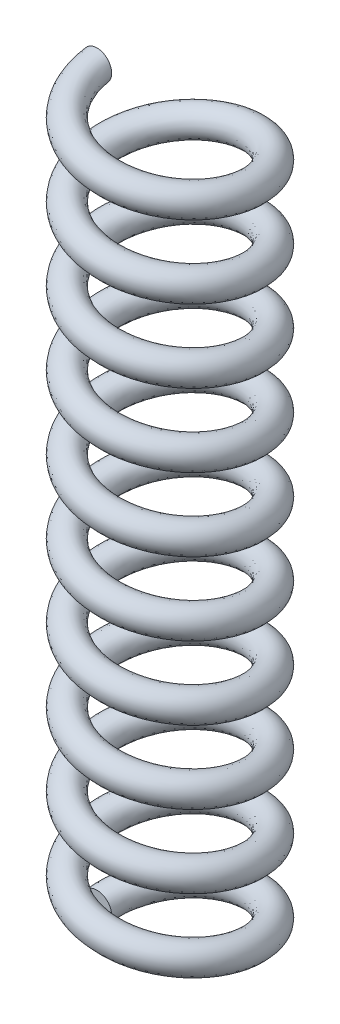
SolidWorks part; units mm, degrees
material "Alliage 1060"
ref_plane "Plan de face" through (0, 0, 0) normal (0, 0, 1) x (1, 0, 0)
ref_plane "Plan de dessus" through (0, 0, 0) normal (0, 1, 0) x (1, 0, 0)
ref_plane "Plan de droite" through (0, 0, 0) normal (1, 0, 0) x (0, 0, -1)
sketch "Esquisse1" plane through (0, 0, 0) normal (0, 1, 0) x (1, 0, 0)
  circle A0 centre (0, 0) radius 10
  dimension "D1" = 20
curve "Hélice/Spirale2" pitch 10 height 100 turns 10
sketch "Esquisse4" plane through (0, 0, 0) normal (0, 0, 1) x (1, 0, 0)
  circle A0 centre (-10, 0) radius 2
  spline S0 degree 3 poles (-10, 0) (-10, 0.207) (-9.4793, 0.6256) (-7.2552, 1.2498) (-3.9265, 1.875) (0, 2.5) (3.9265, 3.125) (7.2552, 3.75) (9.4793, 4.375) (10.2603, 5) (9.4793, 5.625) (7.2552, 6.25) (2.8169, 7.0833) (-2.8169, 7.9167) (-7.2552, 8.75) (-9.4793, 9.375) (-10.2603, 10) (-9.4793, 10.625) (-7.2552, 11.25) (-2.8169, 12.0833) (2.8169, 12.9167) (7.2552, 13.75) (9.4793, 14.375) (10.2603, 15) (9.4793, 15.625) (7.2552, 16.25) (2.8169, 17.0833) (-2.8169, 17.9167) (-7.2552, 18.75) (-9.4793, 19.375) (-10.2603, 20) (-9.4793, 20.625) (-7.2552, 21.25) (-2.8169, 22.0833) (2.8169, 22.9167) (7.2552, 23.75) (9.4793, 24.375) (10.2603, 25) (9.4793, 25.625) (7.2552, 26.25) (2.8169, 27.0833) (-2.8169, 27.9167) (-7.2552, 28.75) (-9.4793, 29.375) (-10.2603, 30) (-9.4793, 30.625) (-7.2552, 31.25) (-2.8169, 32.0833) (2.8169, 32.9167) (7.2552, 33.75) (9.4793, 34.375) (10.2603, 35) (9.4793, 35.625) (7.2552, 36.25) (2.8169, 37.0833) (-2.8169, 37.9167) (-7.2552, 38.75) (-9.4793, 39.375) (-10.2603, 40) (-9.4793, 40.625) (-7.2552, 41.25) (-2.8169, 42.0833) (2.8169, 42.9167) (7.2552, 43.75) (9.4793, 44.375) (10.2603, 45) (9.4793, 45.625) (7.2552, 46.25) (2.8169, 47.0833) (-2.8169, 47.9167) (-7.2552, 48.75) (-9.4793, 49.375) (-10.2603, 50) (-9.4793, 50.625) (-7.2552, 51.25) (-2.8169, 52.0833) (2.8169, 52.9167) (7.2552, 53.75) (9.4793, 54.375) (10.2603, 55) (9.4793, 55.625) (7.2552, 56.25) (2.8169, 57.0833) (-2.8169, 57.9167) (-7.2552, 58.75) (-9.4793, 59.375) (-10.2603, 60) (-9.4793, 60.625) (-7.2552, 61.25) (-2.8169, 62.0833) (2.8169, 62.9167) (7.2552, 63.75) (9.4793, 64.375) (10.2603, 65) (9.4793, 65.625) (7.2552, 66.25) (2.8169, 67.0833) (-2.8169, 67.9167) (-7.2552, 68.75) (-9.4793, 69.375) (-10.2603, 70) (-9.4793, 70.625) (-7.2552, 71.25) (-2.8169, 72.0833) (2.8169, 72.9167) (7.2552, 73.75) (9.4793, 74.375) (10.2603, 75) (9.4793, 75.625) (7.2552, 76.25) (2.8169, 77.0833) (-2.8169, 77.9167) (-7.2552, 78.75) (-9.4793, 79.375) (-10.2603, 80) (-9.4793, 80.625) (-7.2552, 81.25) (-2.8169, 82.0833) (2.8169, 82.9167) (7.2552, 83.75) (9.4793, 84.375) (10.2603, 85) (9.4793, 85.625) (7.2552, 86.25) (2.8169, 87.0833) (-2.8169, 87.9167) (-7.2552, 88.75) (-9.4793, 89.375) (-10.2603, 90) (-9.4793, 90.625) (-7.2552, 91.25) (-2.8169, 92.0833) (2.8169, 92.9167) (7.2552, 93.75) (9.4793, 94.375) (10.2603, 95) (9.4793, 95.625) (7.2552, 96.25) (3.9265, 96.875) (0, 97.5) (-3.9265, 98.125) (-7.2552, 98.7502) (-9.4793, 99.3744) (-10, 99.793) (-10, 100) knots 0 0 0 0 0.00625 0.0125 0.01875 0.025 0.03125 0.0375 0.04375 0.05 0.05625 0.0625 0.06875 0.08125 0.0875 0.09375 0.1 0.10625 0.1125 0.11875 0.13125 0.1375 0.14375 0.15 0.15625 0.1625 0.16875 0.18125 0.1875 0.19375 0.2 0.20625 0.2125 0.21875 0.23125 0.2375 0.24375 0.25 0.25625 0.2625 0.26875 0.28125 0.2875 0.29375 0.3 0.30625 0.3125 0.31875 0.33125 0.3375 0.34375 0.35 0.35625 0.3625 0.36875 0.38125 0.3875 0.39375 0.4 0.40625 0.4125 0.41875 0.43125 0.4375 0.44375 0.45 0.45625 0.4625 0.46875 0.48125 0.4875 0.49375 0.5 0.50625 0.5125 0.51875 0.53125 0.5375 0.54375 0.55 0.55625 0.5625 0.56875 0.58125 0.5875 0.59375 0.6 0.60625 0.6125 0.61875 0.63125 0.6375 0.64375 0.65 0.65625 0.6625 0.66875 0.68125 0.6875 0.69375 0.7 0.70625 0.7125 0.71875 0.73125 0.7375 0.74375 0.75 0.75625 0.7625 0.76875 0.78125 0.7875 0.79375 0.8 0.80625 0.8125 0.81875 0.83125 0.8375 0.84375 0.85 0.85625 0.8625 0.86875 0.88125 0.8875 0.89375 0.9 0.90625 0.9125 0.91875 0.93125 0.9375 0.94375 0.95 0.95625 0.9625 0.96875 0.975 0.98125 0.9875 0.99375 1 1 1 1 construction
  dimension "D1" = 4
sweep "Balayage2" add profiles "Esquisse4" path "Hélice/Spirale2"
